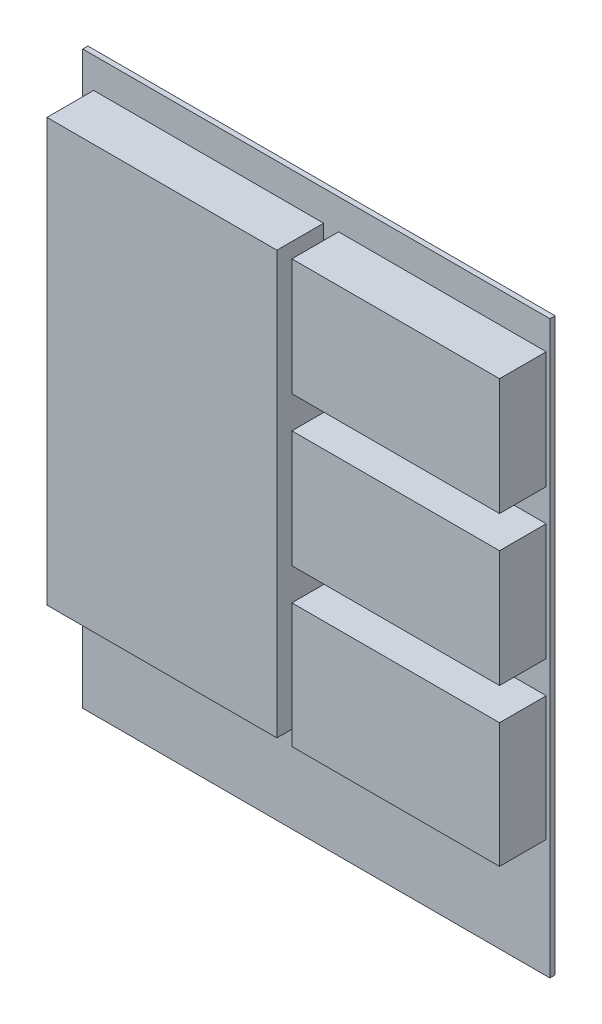
SolidWorks part; units mm, degrees
ref_plane "Front Plane" through (0, 0, 0) normal (0, 0, 1) x (1, 0, 0)
ref_plane "Top Plane" through (0, 0, 0) normal (0, 1, 0) x (1, 0, 0)
ref_plane "Right Plane" through (0, 0, 0) normal (1, 0, 0) x (0, 0, -1)
sketch "Sketch1" plane through (0, 0, 0) normal (0, 0, 1) x (1, 0, 0)
  line L1 (0, 0) -> (180, 0)
  line L2 (0, 0) -> (0, 220)
  line L3 (0, 220) -> (180, 220)
  line L4 (180, 0) -> (180, 220)
  dimension "D1" = 220
  dimension "D2" = 180
extrude "Base" add sketch "Sketch1" along normal blind 2
sketch "Sketch2" plane through (0, 0, 0) normal (0, 0, 1) x (1, 0, 0)
  line L0 (138.5962, 163.278) -> (138.5962, 150.8827) construction
  line L1 (4.2054, 208.278) -> (92.8124, 208.278)
  line L2 (4.2054, 208.278) -> (4.2054, 45.5305)
  line L3 (4.2054, 45.5305) -> (92.8124, 45.5305)
  line L4 (92.8124, 208.278) -> (92.8124, 45.5305)
  line L5 (98.5962, 208.278) -> (178.5962, 208.278)
  line L6 (98.5962, 208.278) -> (98.5962, 163.278)
  line L7 (98.5962, 163.278) -> (178.5962, 163.278)
  line L8 (178.5962, 208.278) -> (178.5962, 163.278)
  line L9 (98.5962, 150.8827) -> (178.5962, 150.8827)
  line L10 (98.5962, 150.8827) -> (98.5962, 105.8827)
  line L11 (98.5962, 105.8827) -> (178.5962, 105.8827)
  line L12 (178.5962, 150.8827) -> (178.5962, 105.8827)
  line L13 (98.5962, 93.4873) -> (178.5962, 93.4873)
  line L14 (98.5962, 93.4873) -> (98.5962, 45.5305)
  line L15 (98.5962, 45.5305) -> (178.5962, 45.5305)
  line L16 (178.5962, 93.4873) -> (178.5962, 45.5305)
  line L17 (138.5962, 105.8827) -> (138.5962, 93.4873) construction
  dimension "D1" = 80
  dimension "D2" = 45
extrude "Boards" add sketch "Sketch2" along normal blind 20
